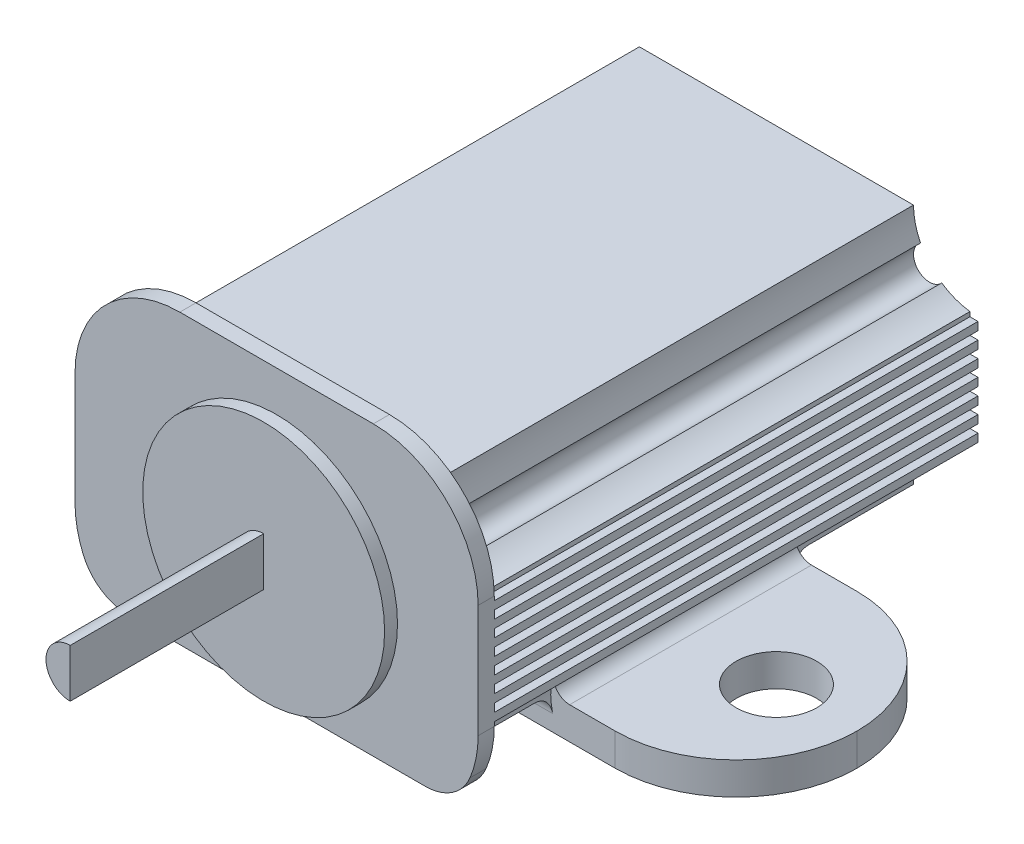
SolidWorks part; units mm, degrees
ref_plane "Front Plane" through (0, 0, 0) normal (0, 0, 1) x (1, 0, 0)
ref_plane "Top Plane" through (0, 0, 0) normal (0, 1, 0) x (1, 0, 0)
ref_plane "Right Plane" through (0, 0, 0) normal (1, 0, 0) x (0, 0, -1)
sketch "Sketch1" plane through (0, 0, 0) normal (0, 0, 1) x (1, 0, 0)
  line L1 (12.5, -7.5) -> (-12.5, -7.5)
  line L2 (12.5, -7.5) -> (12.5, 7.5)
  line L3 (12.5, 7.5) -> (-12.5, 7.5)
  line L4 (-12.5, -7.5) -> (-12.5, 7.5)
  line L5 (12.5, -7.5) -> (-12.5, 7.5) construction
  line L6 (12.5, 7.5) -> (-12.5, -7.5) construction
  point P0 (0, 0)
  dimension "D1" = 25
  dimension "D2" = 15
extrude "Boss-Extrude1" add sketch "Sketch1" along normal blind 30
sketch "Sketch2" plane through (0, 0, 30) normal (0, 0, 1) x (1, 0, 0)
  line L1 (12.5, -10) -> (-12.5, -10)
  line L2 (12.5, -10) -> (12.5, 10)
  line L3 (12.5, 10) -> (-12.5, 10)
  line L4 (-12.5, -10) -> (-12.5, 10)
  line L5 (12.5, -10) -> (-12.5, 10) construction
  line L6 (12.5, 10) -> (-12.5, -10) construction
  point P0 (0, 0)
  dimension "D1" = 25
  dimension "D2" = 20
extrude "Boss-Extrude2" add sketch "Sketch2" along normal blind 1
sketch "Sketch3" plane through (0, 0, 31) normal (0, 0, 1) x (1, 0, 0)
  circle A0 centre (0, 0) radius 7.5
  dimension "D1" = 15
extrude "Boss-Extrude3" add sketch "Sketch3" along normal blind 0.8
sketch "Sketch4" plane through (0, 0, 0) normal (0, 0, -1) x (-1, 0, 0)
  circle A0 centre (-12.5, 7.5) radius 4
  circle A1 centre (12.5, 7.5) radius 4
  circle A2 centre (12.5, -7.5) radius 4
  circle A3 centre (-12.5, -7.5) radius 4
  dimension "D1" = 8
  dimension "D2" = 8
  dimension "D3" = 8
  dimension "D4" = 8
extrude "Cut-Extrude1" cut sketch "Sketch4" against normal up to surface (30 mm away) up to face at (0, -8.75, 30)
sketch "Sketch5" plane through (0, 0, 0) normal (0, 0, -1) x (-1, 0, 0)
  line L0 (-12.5, -3.5) -> (-12.5, -10) construction
  line L1 (-12, 4.25) -> (-13, 4.25)
  line L2 (-12, 4.25) -> (-12, 4.75)
  line L3 (-12, 4.75) -> (-13, 4.75)
  line L4 (-13, 4.25) -> (-13, 4.75)
  line L5 (-12, 4.25) -> (-13, 4.75) construction
  line L6 (-12, 4.75) -> (-13, 4.25) construction
  line L7 (-13, 3.25) -> (-13, 3.75)
  line L8 (-12, 3.75) -> (-13, 3.75)
  line L9 (-12, 3.25) -> (-12, 3.75)
  line L10 (-12, 3.25) -> (-13, 3.25)
  line L11 (-13, 2.25) -> (-13, 2.75)
  line L12 (-12, 2.75) -> (-13, 2.75)
  line L13 (-12, 2.25) -> (-12, 2.75)
  line L14 (-12, 2.25) -> (-13, 2.25)
  line L15 (-13, 1.25) -> (-13, 1.75)
  line L16 (-12, 1.75) -> (-13, 1.75)
  line L17 (-12, 1.25) -> (-12, 1.75)
  line L18 (-12, 1.25) -> (-13, 1.25)
  line L19 (-13, 0.25) -> (-13, 0.75)
  line L20 (-12, 0.75) -> (-13, 0.75)
  line L21 (-12, 0.25) -> (-12, 0.75)
  line L22 (-12, 0.25) -> (-13, 0.25)
  line L23 (-13, -0.75) -> (-13, -0.25)
  line L24 (-12, -0.25) -> (-13, -0.25)
  line L25 (-12, -0.75) -> (-12, -0.25)
  line L26 (-12, -0.75) -> (-13, -0.75)
  line L27 (-13, -1.75) -> (-13, -1.25)
  line L28 (-12, -1.25) -> (-13, -1.25)
  line L29 (-12, -1.75) -> (-12, -1.25)
  line L30 (-12, -1.75) -> (-13, -1.75)
  line L31 (-13, -2.75) -> (-13, -2.25)
  line L32 (-12, -2.25) -> (-13, -2.25)
  line L33 (-12, -2.75) -> (-12, -2.25)
  line L34 (-12, -2.75) -> (-13, -2.75)
  line L35 (-13, -3.75) -> (-13, -3.25)
  line L36 (-12, -3.25) -> (-13, -3.25)
  line L37 (-12, -3.75) -> (-12, -3.25)
  line L38 (-12, -3.75) -> (-13, -3.75)
  line L39 (-13, -4.75) -> (-13, -4.25)
  line L40 (-12, -4.25) -> (-13, -4.25)
  line L41 (-12, -4.75) -> (-12, -4.25)
  line L42 (-12, -4.75) -> (-13, -4.75)
  line L43 (-13, -5.75) -> (-13, -5.25)
  line L44 (-12, -5.25) -> (-13, -5.25)
  line L45 (-12, -5.75) -> (-12, -5.25)
  line L46 (-12, -5.75) -> (-13, -5.75)
  point P0 (-12.5, 4.5)
  dimension "D1" = 1
  dimension "D2" = 1
  dimension "D3" = 0.5
  dimension "D4" = 11
extrude "Cut-Extrude2" cut sketch "Sketch5" against normal up to surface (30 mm away) up to face at (0, -6.7239, 30)
mirror "Mirror1" about plane through (0, 0, 0) normal (1, 0, 0) of "Cut-Extrude2"
sketch "Sketch6" plane through (0, -7.5, 0) normal (0, -1, 0) x (1, 0, 0)
  line L6 (20, 7.5) -> (-20, 7.5)
  line L7 (20, 7.5) -> (20, 22.5)
  line L8 (20, 22.5) -> (-20, 22.5)
  line L9 (-20, 7.5) -> (-20, 22.5)
  line L10 (20, 7.5) -> (-20, 22.5) construction
  line L11 (20, 22.5) -> (-20, 7.5) construction
  point P0 (2.5, 13.5996)
  point P1 (0, 15)
  dimension "D1" = 40
  dimension "D2" = 15
  dimension "D3" = 15
extrude "Boss-Extrude4" add sketch "Sketch6" along normal blind 2
sketch "Sketch7" plane through (0, -9.5, 0) normal (0, -1, 0) x (1, 0, 0)
  line L0 (-20, 22.5) -> (-20, 7.5) construction
  line L1 (20, 7.5) -> (20, 22.5) construction
  circle A0 centre (-15, 15) radius 2.5
  circle A1 centre (15, 15) radius 2.5
  dimension "D1" = 5
  dimension "D2" = 5
  dimension "D3" = 5
  dimension "D4" = 5
extrude "Cut-Extrude3" cut sketch "Sketch7" against normal blind 2
sketch "Sketch8" plane through (0, 0, 31.8) normal (0, 0, 1) x (1, 0, 0)
  line L0 (0, 1.5) -> (0, -1.5)
  arc A0 (0, 1.5) -> (0, -1.5) centre (0, 0) ccw
  dimension "D1" = 3
extrude "Boss-Extrude5" add sketch "Sketch8" along normal blind 12
fillet "Fillet1" radius 6.5 4 edges at (12.5, -10, 30.5) (12.5, 10, 30.5) (-12.5, -10, 30.5) (-12.5, 10, 30.5)
sketch "Sketch9" plane through (0, 0, 31) normal (0, 0, 1) x (1, 0, 0)
  circle A0 centre (-8, 8) radius 1.5
  circle A1 centre (-8, -8) radius 1.5
  circle A2 centre (8, -8) radius 1.5
  circle A3 centre (8, 8) radius 1.5
  dimension "D1" = 3
  dimension "D2" = 3
  dimension "D3" = 3
  dimension "D4" = 3
  dimension "D5" = 8
  dimension "D6" = 8
  dimension "D7" = 8
  dimension "D8" = 8
  dimension "D9" = 8
  dimension "D10" = 8
  dimension "D11" = 8
  dimension "D12" = 8
ref_plane "Plane1" through (3, 0, 0) normal (1, 0, 0) x (0, 0, -1)
fillet "Fillet2" radius 1 2 edges at (-8.5, -7.5, 15) (8.5, -7.5, 15)
fillet "Fillet3" radius 7.5 4 edges at (20, -8.5, 7.5) (20, -8.5, 22.5) (-20, -8.5, 7.5) (-20, -8.5, 22.5)
fillet "Fillet4" radius 1 2 edges at (0, -7.5, 7.5) (0, -7.5, 22.5)
sketch "Sketch11" plane through (0, 0, 0) normal (0, 0, -1) x (-1, 0, 0)
  circle A0 centre (-9.5, 4.8542) radius 1
  arc A1 (-12, 3.5314) -> (-8.5, 7.5) centre (-12.5, 7.5) ccw construction
  circle A2 centre (9.5, 4.8542) radius 1
  arc A3 (8.5, 7.5) -> (12, 3.5314) centre (12.5, 7.5) ccw construction
  circle A4 centre (9.5, -4.8542) radius 1
  arc A5 (12, -3.5314) -> (8.5, -7.5) centre (12.5, -7.5) ccw construction
  circle A6 centre (-15.3284, -4.6716) radius 1
  arc A7 (-12.5, -3.5) -> (-16.5, -7.5) centre (-12.5, -7.5) ccw construction
  dimension "D1" = 2
  dimension "D2" = 2
  dimension "D3" = 2
  dimension "D4" = 2
extrude "Cut-Extrude6" cut sketch "Sketch11" against normal up to surface (30 mm away) up to face at (0, -5.286, 30)
fillet "Fillet5" radius 0.5 2 edges at (0, -7.5, 30) (0, 7.5, 30)
sketch "Sketch12" plane through (0, 0, 30) normal (0, 0, -1) x (-1, 0, 0)
  line L1 (12.5, -7.5) -> (-12.5, -7.5)
  line L2 (12.5, -7.5) -> (12.5, 7.5)
  line L3 (12.5, 7.5) -> (-12.5, 7.5)
  line L4 (-12.5, -7.5) -> (-12.5, 7.5)
  line L5 (12.5, -7.5) -> (-12.5, 7.5) construction
  line L6 (12.5, 7.5) -> (-12.5, -7.5) construction
  point P0 (0, 0)
sketch "Sketch13" plane through (0, 0, 31) normal (0, 0, 1) x (1, 0, 0)
  line L0 (-6, -10) -> (6, -10) construction
  line L1 (17.1842, -12.1409) -> (-17.1842, -12.1409)
  line L2 (17.1842, -12.1409) -> (17.1842, -7.8591)
  line L3 (17.1842, -7.8591) -> (-17.1842, -7.8591)
  line L4 (-17.1842, -12.1409) -> (-17.1842, -7.8591)
  line L5 (17.1842, -12.1409) -> (-17.1842, -7.8591) construction
  line L6 (17.1842, -7.8591) -> (-17.1842, -12.1409) construction
  point P0 (0, -10)
extrude "Cut-Extrude9" cut sketch "Sketch13" against normal blind 3
fillet "Fillet6" radius 3 2 edges at (-10.8217, -7.8591, 30.5) (10.8217, -7.8591, 30.5)
